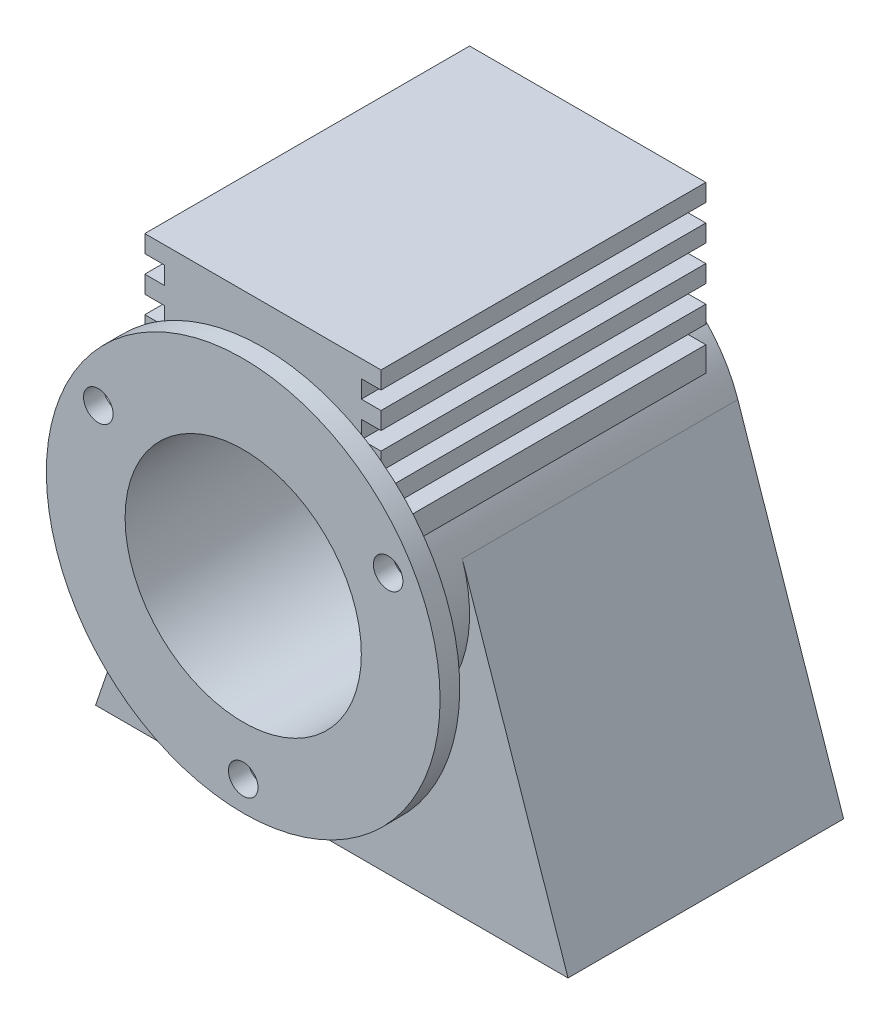
SolidWorks part; units mm, degrees
ref_plane "Front Plane" through (0, 0, 0) normal (0, 0, 1) x (1, 0, 0)
ref_plane "Top Plane" through (0, 0, 0) normal (0, 1, 0) x (1, 0, 0)
ref_plane "Right Plane" through (0, 0, 0) normal (1, 0, 0) x (0, 0, -1)
sketch "Sketch1" plane through (0, 0, 0) normal (0, 0, 1) x (1, 0, 0)
  line L0 (-6, 0) -> (6, 0)
  line L1 (6, 0) -> (3.3126, 7.8798)
  line L2 (0, 0) -> (0, 10.25) construction
  line L3 (-6, 0) -> (-3.3126, 7.8798)
  arc A0 (3.3126, 7.8798) -> (-3.3126, 7.8798) centre (0, 6.75) ccw
  point P8 (0, 10.25)
  dimension "D1" = 3.5
  dimension "D2" = 6
  dimension "D3" = 6.75
extrude "Boss-Extrude1" add sketch "Sketch1" along normal mid plane 7
sketch "Sketch3" plane through (0, 0, 3.5) normal (0, 0, 1) x (1, 0, 0)
  line L0 (-6, 0) -> (6, 0) construction
  circle A0 centre (0, 6.75) radius 5
  circle A1 centre (0, 6.75) radius 3.5
  dimension "D1" = 10
  dimension "D3" = 7
  dimension "D2" = 6.75
extrude "Boss-Extrude2" add sketch "Sketch3" along normal blind 1.75 contours A1 region at (0, 6.75, 3.5)
extrude "Boss-Extrude3" add sketch "Sketch3<3>" along normal blind 0.5 from surface contours A0 starting at face at (3.5, 6.75, 5.25)
sketch "Sketch3<3>" plane through (0, 0, 3.5) normal (0, 0, 1) x (1, 0, 0) same geometry as "Sketch3"
sketch "Sketch4" plane through (0, 0, 5.75) normal (0, 0, 1) x (1, 0, 0)
  circle A0 centre (0, 6.75) radius 3
  circle A1 centre (0, 6.75) radius 5 construction
  dimension "D1" = 6
extrude "Cut-Extrude2" cut sketch "Sketch4" against normal blind 8.25 contours A0
sketch "Sketch5" plane through (0, 0, -3.5) normal (0, 0, -1) x (-1, 0, 0)
  circle A0 centre (0, 6.75) radius 0.75
  circle A1 centre (0, 6.75) radius 3.5 construction
  dimension "D1" = 1.5
extrude "Cut-Extrude3" cut sketch "Sketch5" against normal blind 8.25
ref_plane "Plane1" through (0, 0, 5.25) normal (0, 0, -1) x (-1, 0, 0)
sketch "Sketch6" plane through (0, 0, 5.25) normal (0, 0, -1) x (-1, 0, 0)
  line L0 (0, 6.75) -> (0, 12.75) construction
  line L1 (-3, 12.75) -> (3, 12.75)
  line L2 (3, 12.75) -> (3, 12.3075)
  line L3 (3, 12.3075) -> (2.5, 12.3075)
  line L4 (2.5, 12.3075) -> (2.5, 11.8575)
  line L5 (2.5, 11.8575) -> (3, 11.8575)
  line L6 (3, 11.8575) -> (3, 11.415)
  line L7 (3, 11.415) -> (2.5, 11.415)
  line L8 (2.5, 11.415) -> (2.5, 10.965)
  line L9 (2.5, 10.965) -> (3, 10.965)
  line L10 (3, 10.965) -> (3, 10.5225)
  line L11 (3, 10.5225) -> (2.5, 10.5225)
  line L12 (2.5, 10.5225) -> (2.5, 10.0725)
  line L13 (2.5, 10.0725) -> (3, 10.0725)
  line L14 (3, 10.0725) -> (3, 9.63)
  line L15 (3, 9.63) -> (2.5, 9.63)
  line L16 (2.5, 9.63) -> (2.5, 9.18)
  line L17 (2.5, 9.18) -> (3, 9.18)
  line L18 (3, 9.18) -> (3, 8.5528)
  line L19 (-3, 9.18) -> (-3, 8.5528)
  line L20 (-2.5, 9.18) -> (-3, 9.18)
  line L21 (-2.5, 9.63) -> (-2.5, 9.18)
  line L22 (-3, 9.63) -> (-2.5, 9.63)
  line L23 (-3, 10.0725) -> (-3, 9.63)
  line L24 (-2.5, 10.0725) -> (-3, 10.0725)
  line L25 (-2.5, 10.5225) -> (-2.5, 10.0725)
  line L26 (-3, 10.5225) -> (-2.5, 10.5225)
  line L27 (-3, 10.965) -> (-3, 10.5225)
  line L28 (-2.5, 10.965) -> (-3, 10.965)
  line L29 (-2.5, 11.415) -> (-2.5, 10.965)
  line L30 (-3, 11.415) -> (-2.5, 11.415)
  line L31 (-3, 11.8575) -> (-3, 11.415)
  line L32 (-2.5, 11.8575) -> (-3, 11.8575)
  line L33 (-2.5, 12.3075) -> (-2.5, 11.8575)
  line L34 (-3, 12.3075) -> (-2.5, 12.3075)
  line L35 (-3, 12.75) -> (-3, 12.3075)
  circle A0 centre (0, 6.75) radius 3.5 construction
  circle A1 centre (0, 6.75) radius 5 construction
  arc A2 (3.3126, 7.8798) -> (-3.3126, 7.8798) centre (0, 6.75) ccw construction
  arc A3 (-3, 8.5528) -> (3, 8.5528) centre (0, 6.75) cw
  dimension "D1" = 6
  dimension "D2" = 3
  dimension "D3" = 0.5
  dimension "D4" = 0.45
  dimension "D5" = 2.43
extrude "Boss-Extrude4" add sketch "Sketch6" along normal blind 8.25 contours L21 A3 L16 L15 L14 L13 L12 L11 L10 L9 L8 L7 L6 L5 L4 L3 L2 L1 L35 L34 L33 L32 L31 L30 L29 L28 L27 L26 L25 L24 L23 L22 | L17 A3 L18 | L19 A3 L20 region at (-2.8459, 8.9793, 5.25) region at (2.8459, 8.9793, 5.25) region at (0, 11.3061, 5.25)
sketch "Sketch7" plane through (0, 0, 5.75) normal (0, 0, 1) x (1, 0, 0)
  line L0 (0, 6.75) -> (5, 6.75) construction
  line L1 (0, 6.75) -> (3.6806, 8.875) construction
  circle A0 centre (0, 6.75) radius 4.25 construction
  circle A1 centre (0, 2.5) radius 0.375
  circle A2 centre (3.6806, 8.875) radius 0.375
  circle A3 centre (-3.6806, 8.875) radius 0.375
  circle A4 centre (0, 6.75) radius 5 construction
  dimension "D1" = 8.5
  dimension "D2" = 0.75
  dimension "D3" = 30
extrude "Cut-Extrude4" cut sketch "Sketch7" against normal up to next
